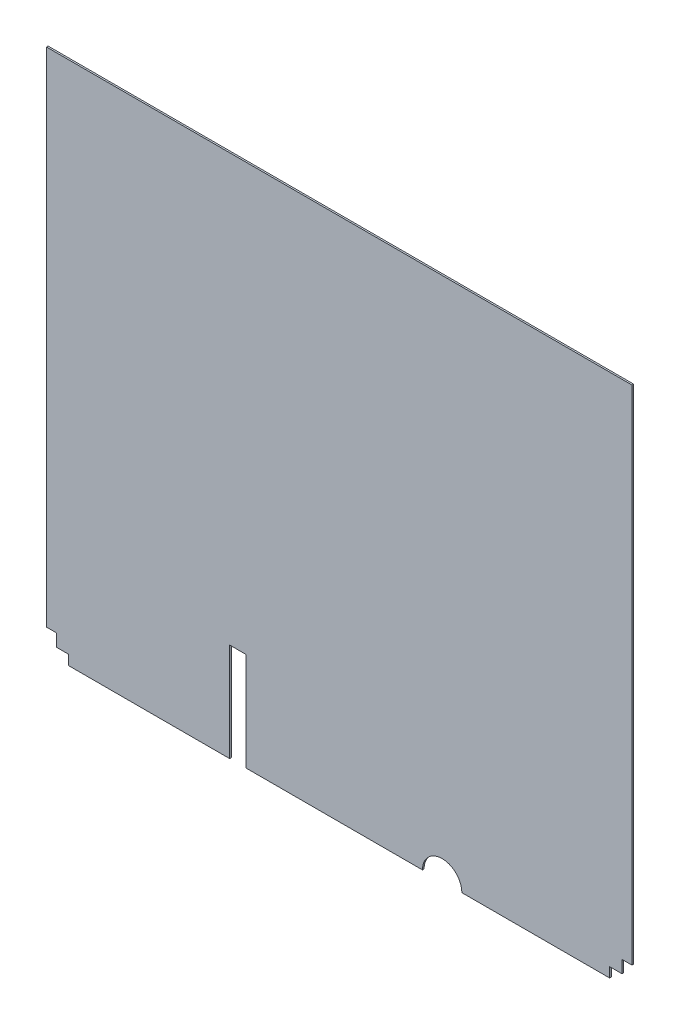
SolidWorks part; units mm, degrees
ref_plane "Front Plane" through (0, 0, 0) normal (0, 0, 1) x (1, 0, 0)
ref_plane "Top Plane" through (0, 0, 0) normal (0, 1, 0) x (1, 0, 0)
ref_plane "Right Plane" through (0, 0, 0) normal (1, 0, 0) x (0, 0, -1)
sketch "Sketch1" plane through (0, 0, 0) normal (0, 0, 1) x (1, 0, 0)
  line L0 (0, 34.544) -> (15.24, 34.544)
  line L1 (0, 0) -> (907.001, 0)
  line L2 (0, 0) -> (0, 812.8)
  line L3 (0, 812.8) -> (907.001, 812.8)
  line L4 (907.001, 0) -> (907.001, 812.8)
  line L5 (0, 0) -> (914.4, 0) construction
  line L6 (0, 0) -> (0, 914.4) construction
  line L7 (0, 914.4) -> (914.4, 914.4) construction
  line L8 (914.4, 0) -> (914.4, 914.4) construction
  line L9 (15.24, 34.544) -> (15.24, 15.24)
  line L10 (15.24, 15.24) -> (34.544, 15.24)
  line L11 (34.544, 15.24) -> (34.544, 0)
  line L12 (907.001, 34.544) -> (891.761, 34.544)
  line L13 (891.761, 34.544) -> (891.761, 15.24)
  line L14 (891.761, 15.24) -> (872.457, 15.24)
  line L15 (872.457, 15.24) -> (872.457, 0)
  line L16 (283.8375, 0) -> (283.8375, 152.4)
  line L17 (283.8375, 152.4) -> (309.2375, 152.4)
  line L18 (309.2375, 152.4) -> (309.2375, 0)
  arc A0 (643.4983, 0) -> (582.5383, 0) centre (613.0183, 0) ccw
  dimension "D13" = 30.48
  dimension "D1" = 812.8
  dimension "D2" = 907.001
  dimension "D3" = 914.4
  dimension "D4" = 914.4
  dimension "D5" = 15.24
  dimension "D6" = 15.24
  dimension "D7" = 34.544
  dimension "D8" = 34.544
  dimension "D9" = 15.24
  dimension "D10" = 15.24
  dimension "D11" = 34.544
  dimension "D12" = 34.544
  dimension "D14" = 152.4
  dimension "D15" = 25.4
extrude "Boss-Extrude1" add sketch "Sketch1" along normal blind 2.54 contours L15 L14 L13 L12 L4 L3 L2 L0 L9 L10 L11 L1 region at (454.0138, 409.8191, 0)
